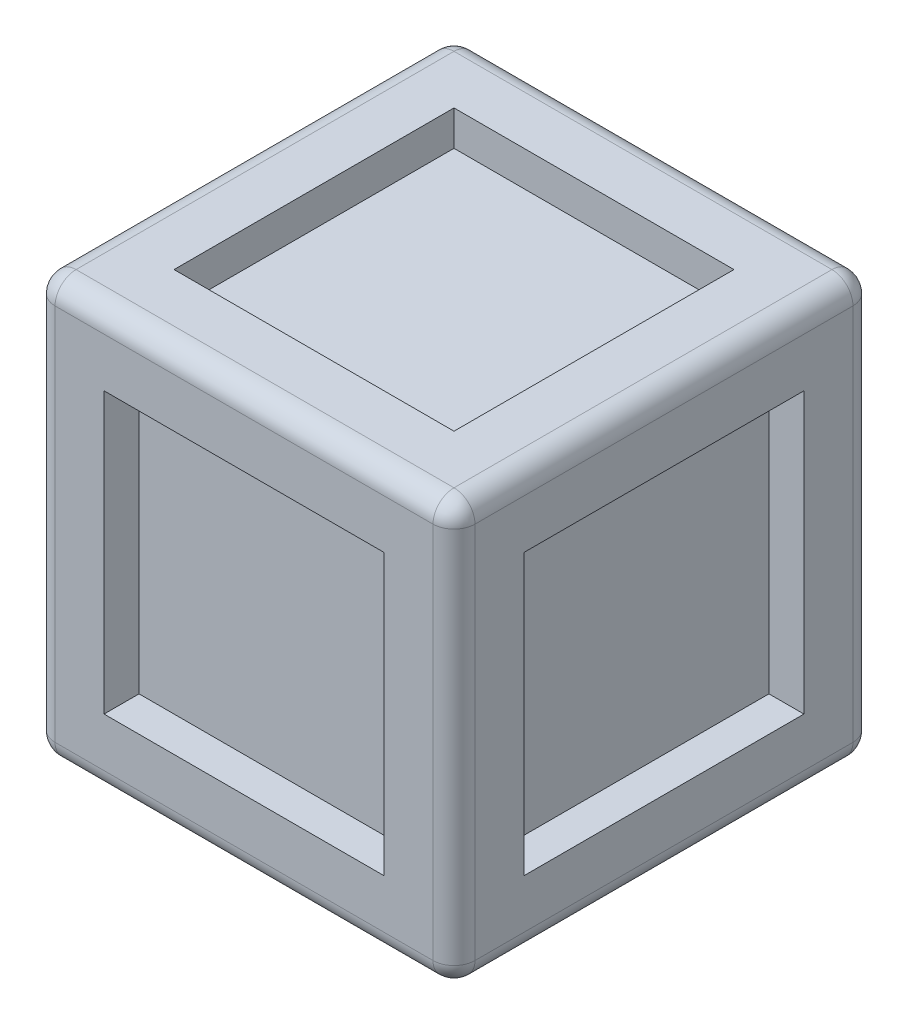
SolidWorks part; units mm, degrees
ref_plane "Płaszczyzna przednia" through (0, 0, 0) normal (0, 0, 1) x (1, 0, 0)
ref_plane "Płaszczyzna górna" through (0, 0, 0) normal (0, 1, 0) x (1, 0, 0)
ref_plane "Płaszczyzna prawa" through (0, 0, 0) normal (1, 0, 0) x (0, 0, -1)
sketch "Szkic1" plane through (0, 0, 0) normal (0, 0, 1) x (1, 0, 0)
  line L1 (30, -30) -> (-30, -30)
  line L2 (30, -30) -> (30, 30)
  line L3 (30, 30) -> (-30, 30)
  line L4 (-30, -30) -> (-30, 30)
  line L5 (30, -30) -> (-30, 30) construction
  line L6 (30, 30) -> (-30, -30) construction
  point P0 (0, 0)
  dimension "D1" = 60
extrude "Dodanie-wyciągnięcie1" add sketch "Szkic1" along normal blind 30 and the other way blind 30
fillet "Zaokrąglenie1" radius 3 12 edges at (-30, -30, 0) (0, -30, -30) (-30, 0, -30) (30, 0, -30) (30, -30, 0) (0, 30, -30) (30, 30, 0) (-30, 30, 0) (0, 30, 30) (30, 0, 30) (0, -30, 30) (-30, 0, 30)
sketch "Szkic2" plane through (0, 0, 30) normal (0, 0, 1) x (1, 0, 0)
  line L8 (20, -20) -> (20, 20)
  line L9 (20, -20) -> (20, 20)
  line L10 (20, 20) -> (-20, 20)
  line L11 (20, 20) -> (-20, 20)
  line L16 (-20, 20) -> (-20, -20)
  line L17 (-20, 20) -> (-20, -20)
  line L18 (-20, -20) -> (20, -20)
  line L19 (-20, -20) -> (20, -20)
  dimension "D1" = 7
extrude "Wytnij-wyciągnięcie1" cut sketch "Szkic2" against normal blind 5
ref_axis "Oś1" through (-33, 0, 0) along (1, 0, 0)
ref_axis "Oś2" through (0, 0, 33) along (0, 0, -1)
pattern_circular "Szyk kołowy1" count 4 over 360 about axis through (-33, 0, 0) along (1, 0, 0) of "Wytnij-wyciągnięcie1"
pattern_circular "Szyk kołowy2" count 4 over 360 about axis through (0, 0, 25) along (0, 0, 1) of "Szyk kołowy1"
